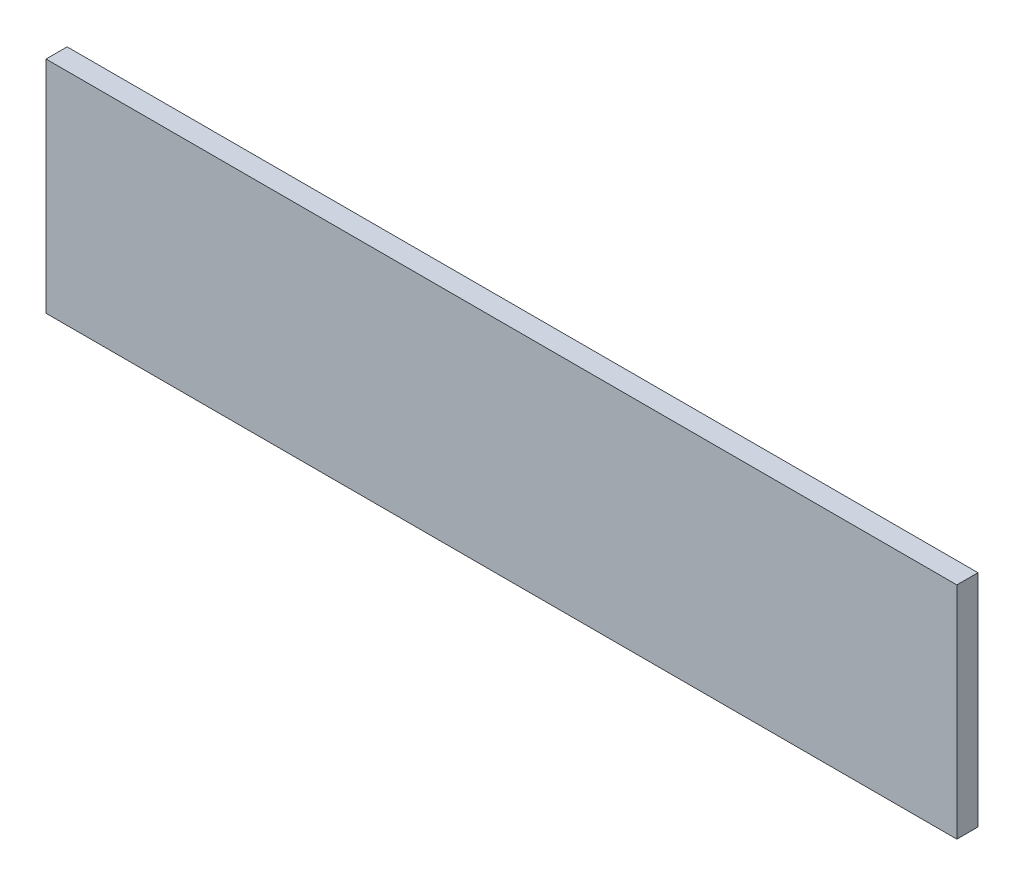
SolidWorks part; units mm, degrees
ref_plane "Plan de face" through (0, 0, 0) normal (0, 0, 1) x (1, 0, 0)
ref_plane "Plan de dessus" through (0, 0, 0) normal (0, 1, 0) x (1, 0, 0)
ref_plane "Plan de droite" through (0, 0, 0) normal (1, 0, 0) x (0, 0, -1)
sketch "Esquisse1" plane through (0, 0, 0) normal (0, 0, 1) x (1, 0, 0)
  line L1 (0, 0) -> (819, 0)
  line L2 (0, 0) -> (0, 198)
  line L3 (0, 198) -> (819, 198)
  line L4 (819, 0) -> (819, 198)
  dimension "D1" = 198
  dimension "D2" = 819
extrude "Boss.-Extru.1" add sketch "Esquisse1" along normal blind 19
sketch "Esquisse2" plane through (0, 198, 0) normal (0, 1, 0) x (1, 0, 0)
  line L0 (0, -19) -> (0, 0) construction
  line L1 (819, -19) -> (0, -19) construction
  point P0 (410, -9.5132)
  point P3 (409.5, -19)
  dimension "D1" = 410
  dimension "D2" = 9.5
ref_axis "Axe1" through (410, 198, 9.5132) along (0, 1, 0)
